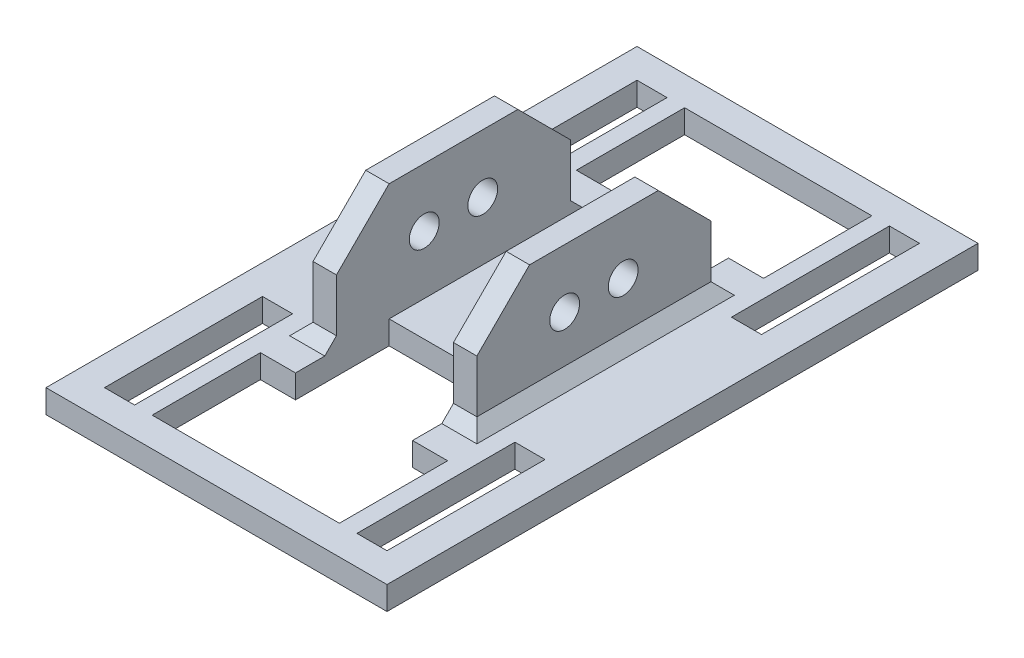
SolidWorks part; units mm, degrees
ref_plane "Front Plane" through (0, 0, 0) normal (0, 0, 1) x (1, 0, 0)
ref_plane "Top Plane" through (0, 0, 0) normal (0, 1, 0) x (1, 0, 0)
ref_plane "Right Plane" through (0, 0, 0) normal (1, 0, 0) x (0, 0, -1)
sketch "Sketch1" plane through (0, 0, 0) normal (0, 1, 0) x (1, 0, 0)
  line L0 (-5, 96) -> (-5, -5)
  line L1 (0, 91) -> (5.14, 91)
  line L2 (0, 91) -> (0, 64)
  line L3 (0, 64) -> (5.14, 64)
  line L4 (5.14, 91) -> (5.14, 64)
  line L5 (43.14, 91) -> (48.28, 91)
  line L6 (43.14, 91) -> (43.14, 64)
  line L7 (43.14, 64) -> (48.28, 64)
  line L8 (48.28, 91) -> (48.28, 64)
  line L9 (0, 27) -> (5.14, 27)
  line L10 (0, 27) -> (0, 0)
  line L11 (0, 0) -> (5.14, 0)
  line L12 (5.14, 27) -> (5.14, 0)
  line L13 (43.14, 27) -> (48.28, 27)
  line L14 (43.14, 27) -> (43.14, 0)
  line L15 (43.14, 0) -> (48.28, 0)
  line L16 (48.28, 27) -> (48.28, 0)
  line L21 (-5, -5) -> (53.28, -5)
  line L22 (53.28, 96) -> (53.28, -5)
  line L23 (-5, 96) -> (53.28, 96)
  dimension "D1" = 37
  dimension "D2" = 5.14
  dimension "D3" = 27
  dimension "D4" = 38
  dimension "D5" = 5
  dimension "D6" = 5
  dimension "D7" = 5
  dimension "D8" = 5
extrude "Boss-Extrude1" add sketch "Sketch1" along normal blind 4
sketch "Sketch2" plane through (0, 4, 0) normal (0, 1, 0) x (1, 0, 0)
  line L0 (24.14, 96) -> (24.14, -5) construction
  line L1 (53.28, 96) -> (-5, 96) construction
  line L2 (-5, -5) -> (53.28, -5) construction
  line L3 (-5, 45.5) -> (53.28, 45.5) construction
  line L4 (14.14, 65.5) -> (34.14, 65.5) construction
  line L5 (14.14, 65.5) -> (14.14, 25.5) construction
  line L6 (14.14, 25.5) -> (34.14, 25.5) construction
  line L7 (34.14, 65.5) -> (34.14, 25.5) construction
  line L8 (-5, 96) -> (-5, -5) construction
  line L9 (53.28, -5) -> (53.28, 96) construction
  line L11 (14.14, 65.5) -> (10.14, 65.5)
  line L12 (14.14, 65.5) -> (14.14, 25.5)
  line L13 (14.14, 25.5) -> (10.14, 25.5)
  line L14 (10.14, 65.5) -> (10.14, 25.5)
  line L15 (34.14, 65.5) -> (38.14, 65.5)
  line L16 (34.14, 65.5) -> (34.14, 25.5)
  line L17 (34.14, 25.5) -> (38.14, 25.5)
  line L18 (38.14, 65.5) -> (38.14, 25.5)
  dimension "D1" = 20
  dimension "D2" = 40
  dimension "D3" = 20
  dimension "D4" = 4
extrude "Boss-Extrude2" add sketch "Sketch2" along normal blind 20
sketch "Sketch3" plane through (38.14, 0, 0) normal (1, 0, 0) x (0, 0, -1)
  line L0 (25.5, 14) -> (65.5, 14) construction
  line L1 (25.5, 24) -> (25.5, 4) construction
  line L2 (65.5, 24) -> (65.5, 4) construction
  circle A0 centre (40.5, 14) radius 2.55
  circle A1 centre (50.5, 14) radius 2.55
  dimension "D1" = 5.1
  dimension "D2" = 10
  dimension "D3" = 15
extrude "Cut-Extrude1" cut sketch "Sketch3" against normal up to surface (28 mm away) up to face at (10.14, 14, -45.5)
chamfer "Chamfer1" distance 2 angle 45 6 edges at (12.14, 4, -65.5) (10.14, 4, -45.5) (12.14, 4, -25.5) (36.14, 4, -65.5) (36.14, 4, -25.5) (38.14, 4, -45.5)
sketch "Sketch4" plane through (10.14, 0, 0) normal (-1, 0, 0) x (0, 0, 1)
  line L0 (-56.5, 24) -> (-65.5, 15)
  line L1 (-65.5, 24) -> (-25.5, 24) construction
  line L2 (-65.5, 24) -> (-65.5, 6) construction
  line L3 (-65.5, 15) -> (-65.5, 24)
  line L4 (-65.5, 24) -> (-56.5, 24)
  line L5 (-34.5, 24) -> (-25.5, 15)
  line L6 (-25.5, 24) -> (-25.5, 6) construction
  line L7 (-25.5, 15) -> (-25.5, 24)
  line L8 (-25.5, 24) -> (-34.5, 24)
  dimension "D1" = 45
extrude "Cut-Extrude2" cut sketch "Sketch4" against normal up to surface (28 mm away) up to face at (38.14, 14, -43.05)
sketch "Sketch5" plane through (0, 4, 0) normal (0, 1, 0) x (1, 0, 0)
  line L0 (8.14, 67.5) -> (14.14, 67.5) construction
  line L1 (34.14, 67.5) -> (40.14, 67.5) construction
  line L2 (40.14, 23.5) -> (34.14, 23.5) construction
  line L3 (14.14, 23.5) -> (8.14, 23.5) construction
  line L4 (34.14, 67.5) -> (34.14, 23.5) construction
  line L5 (14.14, 23.5) -> (14.14, 67.5) construction
  line L6 (8.14, 67.5) -> (14.14, 67.5)
  line L7 (34.14, 67.5) -> (40.14, 67.5)
  line L8 (40.14, 23.5) -> (34.14, 23.5)
  line L9 (14.14, 23.5) -> (8.14, 23.5)
  line L10 (34.14, 67.5) -> (34.14, 56.5)
  line L11 (14.14, 23.5) -> (14.14, 34.5)
  line L12 (5.14, 91) -> (0, 91) construction
  line L13 (8.14, 91) -> (40.14, 91)
  line L14 (14.14, 72.5) -> (14.14, 56.5)
  line L15 (8.14, 0) -> (40.14, 0)
  line L16 (34.14, 72.5) -> (34.14, 56.5)
  line L17 (0, 0) -> (5.14, 0) construction
  line L18 (40.14, 67.5) -> (40.14, 23.5) construction
  line L21 (14.14, 18.5) -> (8.14, 18.5)
  line L22 (8.14, 0) -> (8.14, 18.5)
  line L25 (34.14, 18.5) -> (40.14, 18.5)
  line L26 (40.14, 0) -> (40.14, 18.5)
  line L29 (14.14, 72.5) -> (8.14, 72.5)
  line L30 (8.14, 91) -> (8.14, 72.5)
  line L33 (34.14, 72.5) -> (40.14, 72.5)
  line L34 (40.14, 91) -> (40.14, 72.5)
  line L35 (8.14, 23.5) -> (8.14, 67.5) construction
  line L36 (14.14, 56.5) -> (34.14, 56.5)
  line L37 (14.14, 34.5) -> (34.14, 34.5)
  line L38 (14.14, 56.5) -> (14.14, 67.5)
  line L39 (34.14, 34.5) -> (34.14, 23.5)
  line L40 (34.14, 34.5) -> (34.14, 18.5)
  line L41 (14.14, 34.5) -> (14.14, 18.5)
  line M24 (14.14, 67.5) -> (14.14, 23.5)
  line M48 (34.14, 23.5) -> (34.14, 67.5)
  dimension "D1" = 5
  dimension "D2" = 5
extrude "Cut-Extrude3" cut sketch "Sketch5" along direction (0, -1, 0) on the side against the normal up to surface (4 mm away) contours L34 L13 L30 L29 L14 L21 L22 L15 L26 L25 L16 L33 M24 M48 | L41 L21 L22 L15 L26 L25 L40 L37 M24 M48 region at (24.14, 4, -75.6974) region at (24.14, 4, -15.3026) up to face at (24.14, 0, -45.5)
